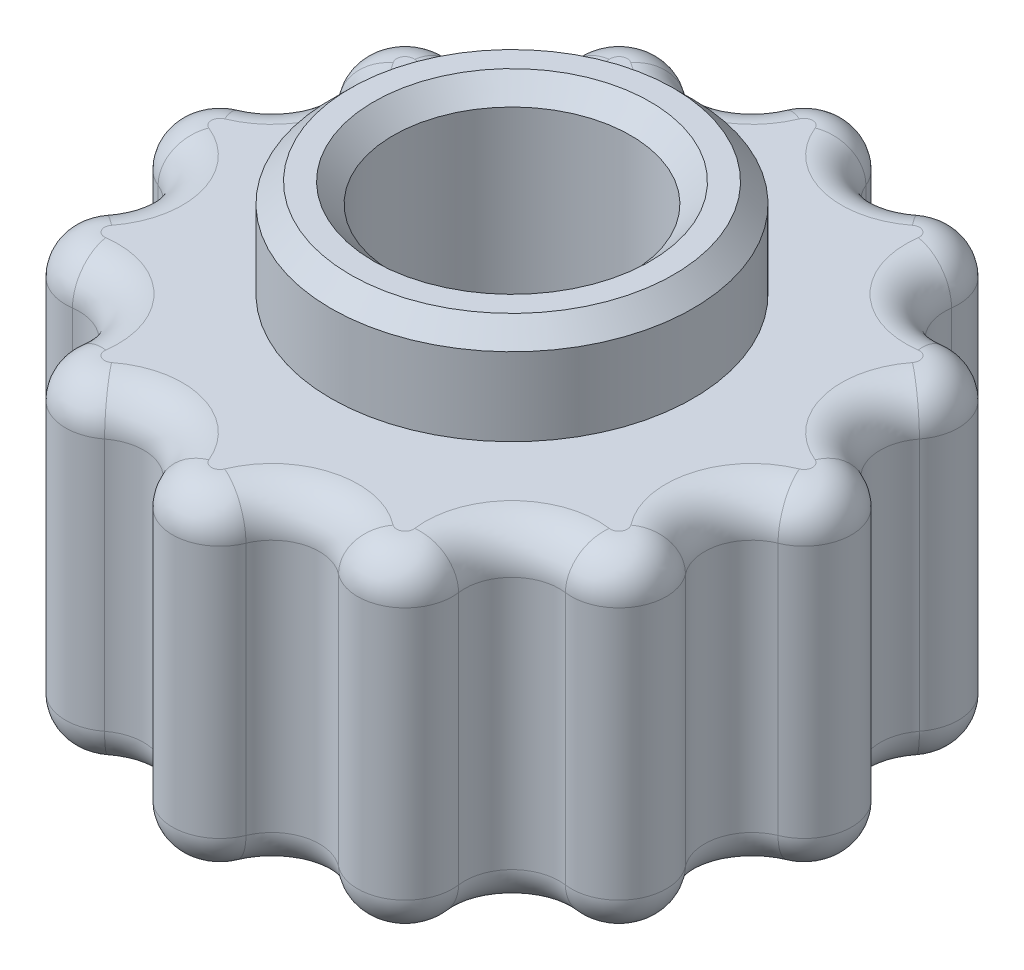
SolidWorks part; units mm, degrees
ref_plane "Спереди" through (0, 0, 0) normal (0, 0, 1) x (1, 0, 0)
ref_plane "Сверху" through (0, 0, 0) normal (0, 1, 0) x (1, 0, 0)
ref_plane "Справа" through (0, 0, 0) normal (1, 0, 0) x (0, 0, -1)
sketch "Эскиз1" plane through (0, 0, 0) normal (0, 1, 0) x (1, 0, 0)
  line L0 (0, -1.2329) -> (0, 7.1561) construction
  line L1 (0, 0) -> (2.9426, 10.982) construction
  circle A0 centre (0, 0) radius 7.5 construction
  arc A1 (1.1283, 7.9608) -> (-1.1283, 7.9608) centre (0, 7.5) ccw
  arc A2 (1.1283, 7.9608) -> (3.0033, 7.4584) centre (2.2566, 8.4217) ccw
  arc A3 (4.9576, 6.3301) -> (3.0033, 7.4584) centre (3.75, 6.4952) ccw
  arc A4 (4.9576, 6.3301) -> (6.3301, 4.9576) centre (6.1651, 6.1651) ccw
  arc A5 (7.4584, 3.0033) -> (6.3301, 4.9576) centre (6.4952, 3.75) ccw
  arc A6 (7.4584, 3.0033) -> (7.9608, 1.1283) centre (8.4217, 2.2566) ccw
  arc A7 (7.9608, -1.1283) -> (7.9608, 1.1283) centre (7.5, 0) ccw
  arc A8 (7.9608, -1.1283) -> (7.4584, -3.0033) centre (8.4217, -2.2566) ccw
  arc A9 (6.3301, -4.9576) -> (7.4584, -3.0033) centre (6.4952, -3.75) ccw
  arc A10 (6.3301, -4.9576) -> (4.9576, -6.3301) centre (6.1651, -6.1651) ccw
  arc A11 (3.0033, -7.4584) -> (4.9576, -6.3301) centre (3.75, -6.4952) ccw
  arc A12 (3.0033, -7.4584) -> (1.1283, -7.9608) centre (2.2566, -8.4217) ccw
  arc A13 (-1.1283, -7.9608) -> (1.1283, -7.9608) centre (0, -7.5) ccw
  arc A14 (-1.1283, -7.9608) -> (-3.0033, -7.4584) centre (-2.2566, -8.4217) ccw
  arc A15 (-4.9576, -6.3301) -> (-3.0033, -7.4584) centre (-3.75, -6.4952) ccw
  arc A16 (-4.9576, -6.3301) -> (-6.3301, -4.9576) centre (-6.1651, -6.1651) ccw
  arc A17 (-7.4584, -3.0033) -> (-6.3301, -4.9576) centre (-6.4952, -3.75) ccw
  arc A18 (-7.4584, -3.0033) -> (-7.9608, -1.1283) centre (-8.4217, -2.2566) ccw
  arc A19 (-7.9608, 1.1283) -> (-7.9608, -1.1283) centre (-7.5, 0) ccw
  arc A20 (-7.9608, 1.1283) -> (-7.4584, 3.0033) centre (-8.4217, 2.2566) ccw
  arc A21 (-6.3301, 4.9576) -> (-7.4584, 3.0033) centre (-6.4952, 3.75) ccw
  arc A22 (-6.3301, 4.9576) -> (-4.9576, 6.3301) centre (-6.1651, 6.1651) ccw
  arc A23 (-3.0033, 7.4584) -> (-4.9576, 6.3301) centre (-3.75, 6.4952) ccw
  arc A24 (-3.0033, 7.4584) -> (-1.1283, 7.9608) centre (-2.2566, 8.4217) ccw
  point P32 (1.6835, 0.972)
  point P57 (0, 0)
  dimension "D1" = 15
  dimension "D2" = 15
  dimension "D3" = 12
extrude "Бобышка-Вытянуть1" add sketch "Эскиз1" along normal blind 8.5 contours A24 A23 A22 A21 A20 A19 A18 A17 A16 A15 A14 A13 A12 A11 A10 A9 A8 A7 A6 A5 A4 A3 A2 A1
sketch "Эскиз2" plane through (0, 8.5, 0) normal (0, 1, 0) x (1, 0, 0)
  circle A0 centre (0, 0) radius 4.65
  dimension "D1" = 9.3
extrude "Бобышка-Вытянуть2" add sketch "Эскиз2" along normal blind 2.5
fillet "Скругление1" radius 1 48 edges at (7.5507, 8.5, -4.3594) (5.3033, 8.5, -5.3033) (4.3594, 8.5, -7.5507) (1.9411, 8.5, -7.2444) (0, 8.5, -8.7188) (-1.9411, 8.5, -7.2444) (-4.3594, 8.5, -7.5507) (-5.3033, 8.5, -5.3033) (-7.5507, 8.5, -4.3594) (-7.2444, 8.5, -1.9411) (-8.7188, 8.5, 0) (-7.2444, 8.5, 1.9411) (-7.5507, 8.5, 4.3594) (-5.3033, 8.5, 5.3033) (-4.3594, 8.5, 7.5507) (-1.9411, 8.5, 7.2444) (0, 8.5, 8.7188) (1.9411, 8.5, 7.2444) (4.3594, 8.5, 7.5507) (5.3033, 8.5, 5.3033) (7.5507, 8.5, 4.3594) (7.2444, 8.5, 1.9411) (8.7188, 8.5, 0) (7.5507, 0, -4.3594) (5.3033, 0, -5.3033) (4.3594, 0, -7.5507) (1.9411, 0, -7.2444) (0, 0, -8.7188) (-1.9411, 0, -7.2444) (-4.3594, 0, -7.5507) (-5.3033, 0, -5.3033) (-7.5507, 0, -4.3594) (-7.2444, 0, -1.9411) (-8.7188, 0, 0) (-7.2444, 0, 1.9411) (-7.5507, 0, 4.3594) (-5.3033, 0, 5.3033) (-4.3594, 0, 7.5507) (-1.9411, 0, 7.2444) (0, 0, 8.7188) (1.9411, 0, 7.2444) (4.3594, 0, 7.5507) (5.3033, 0, 5.3033) (7.5507, 0, 4.3594) (7.2444, 0, 1.9411) (8.7188, 0, 0) (7.2444, 8.5, -1.9411) (7.2444, 0, -1.9411)
sketch "Эскиз3" plane through (0, 11, 0) normal (0, 1, 0) x (1, 0, 0)
  circle A0 centre (0, 0) radius 3.05
  dimension "D1" = 6.1
extrude "Вырез-Вытянуть1" cut sketch "Эскиз3" against normal blind 10
chamfer "Фаска1" distance 0.5 angle 45 2 edges at (0, 11, 4.65) (0, 11, 3.05)
